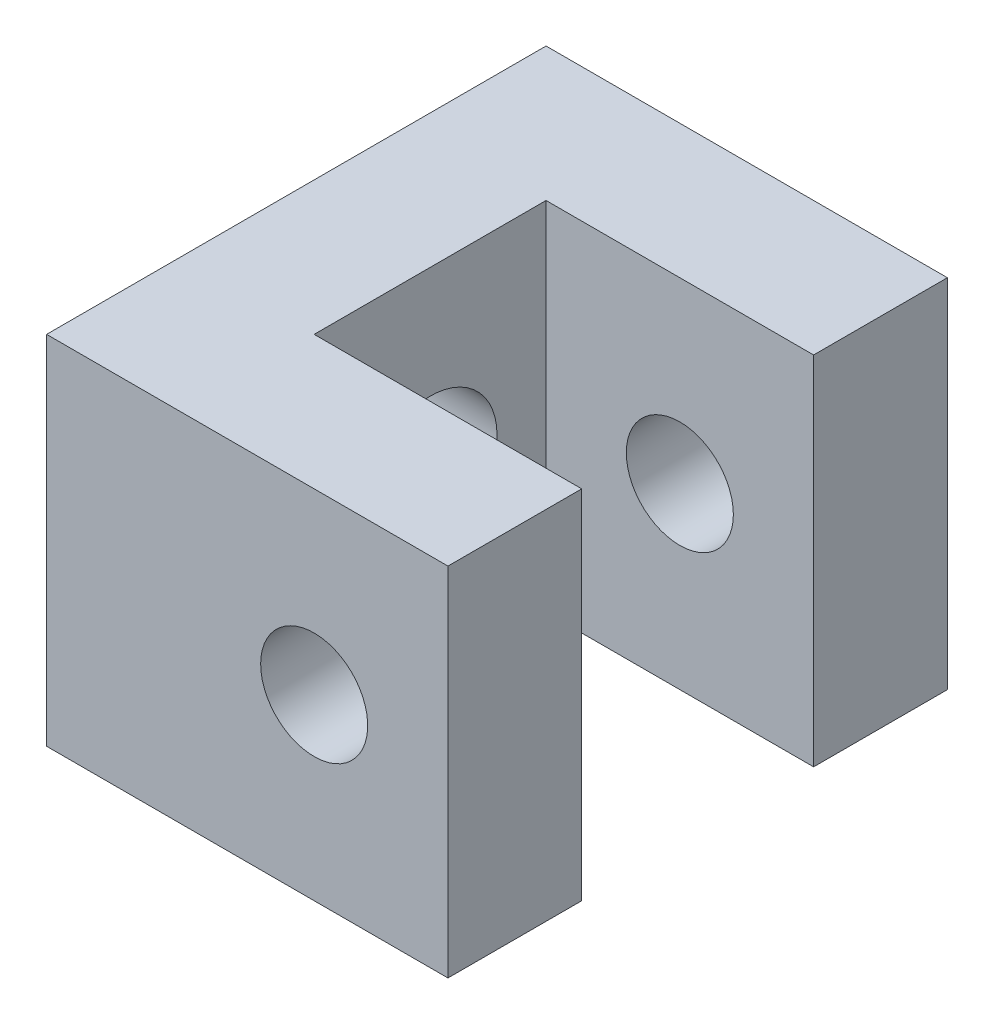
SolidWorks part; units mm, degrees
material "1023 Carbon Steel Sheet (SS)"
ref_plane "Front Plane" through (0, 0, 0) normal (0, 0, 1) x (1, 0, 0)
ref_plane "Top Plane" through (0, 0, 0) normal (0, 1, 0) x (1, 0, 0)
ref_plane "Right Plane" through (0, 0, 0) normal (1, 0, 0) x (0, 0, -1)
sketch "Sketch1" plane through (0, 0, 0) normal (1, 0, 0) x (0, 0, -1)
  line L1 (-28, -20) -> (28, -20)
  line L2 (-28, -20) -> (-28, 20)
  line L3 (-28, 20) -> (28, 20)
  line L4 (28, -20) -> (28, 20)
  line L5 (-28, -20) -> (28, 20) construction
  line L6 (-28, 20) -> (28, -20) construction
  line L7 (-13, -20) -> (13, -20)
  line L8 (-13, -20) -> (-13, 20)
  line L9 (-13, 20) -> (13, 20)
  line L10 (13, -20) -> (13, 20)
  line L11 (-13, -20) -> (13, 20) construction
  line L12 (-13, 20) -> (13, -20) construction
  circle A0 centre (0, 0) radius 7.5
  point P0 (0, 0)
  dimension "D1" = 15
  dimension "D2" = 56
  dimension "D3" = 40
  dimension "D4" = 15
extrude "Boss-Extrude1" add sketch "Sketch1" against normal blind 15 contours L1 L8 L3 L2 | L1 L10 L3 L8 A0 | L10 L1 L4 L3 region at (0, 0, 20.5) region at (0, 0, 12.5229) region at (0, 0, -20.5)
extrude "Boss-Extrude2" add sketch "Sketch1<3>" along normal blind 30 contours L1 L8 L3 L2 | L10 L1 L4 L3 region at (0, 0, 20.5) region at (0, 0, -20.5)
sketch "Sketch1<3>" plane through (0, 0, 0) normal (1, 0, 0) x (0, 0, -1) same geometry as "Sketch1"
sketch "Sketch2" plane through (0, 0, 13) normal (0, 0, -1) x (-1, 0, 0)
  line L0 (-15, 20) -> (-15, -20) construction
  line L1 (-30, 20) -> (0, 20) construction
  line L2 (-30, -20) -> (0, -20) construction
  line L3 (0, -20) -> (0, 20) construction
  circle A0 centre (-15, 0) radius 6
  dimension "D2" = 12
  dimension "D1" = 15
extrude "Cut-Extrude1" cut sketch "Sketch2" against normal through all both and the other way through all
equation "\"CableGuideDepth\"=15"
equation "\"D1@Sketch2\"=\"CableGuideDepth\""
equation "\"CarriageWidth\"=56"
equation "\"D2@Sketch1\"=\"CarriageWidth\""
